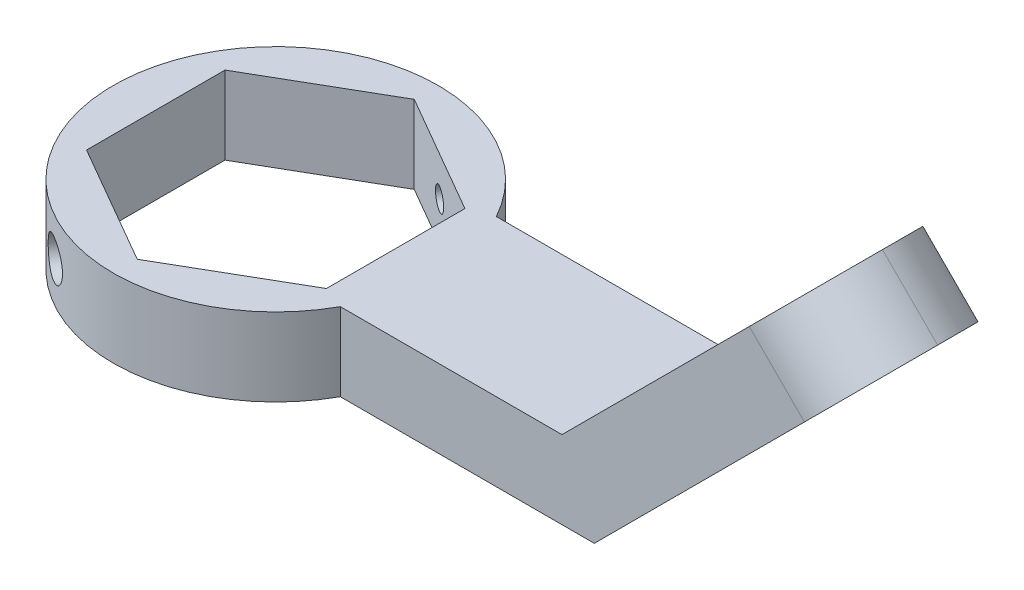
SolidWorks part; units mm, degrees
ref_plane "Front Plane" through (0, 0, 0) normal (0, 0, 1) x (1, 0, 0)
ref_plane "Top Plane" through (0, 0, 0) normal (0, 1, 0) x (1, 0, 0)
ref_plane "Right Plane" through (0, 0, 0) normal (1, 0, 0) x (0, 0, -1)
sketch "Sketch2" plane through (0, 0, 0) normal (0, 0, 1) x (1, 0, 0)
  line L0 (0, 0) -> (61, 0) construction
  line L1 (61, 0) -> (90.5, 29.5) construction
  dimension "D1" = 29.5
  dimension "D2" = 90.5
  dimension "D3" = 45
sketch "Sketch3" plane through (0, 0, 0) normal (0, 1, 0) x (1, 0, 0)
  line L1 (0, 21.3042) -> (-18.45, 10.6521)
  line L2 (-18.45, 10.6521) -> (-18.45, -10.6521)
  line L3 (-18.45, -10.6521) -> (0, -21.3042)
  line L4 (0, -21.3042) -> (18.45, -10.6521)
  line L5 (18.45, -10.6521) -> (18.45, 10.6521)
  line L6 (18.45, 10.6521) -> (0, 21.3042)
  line L7 (-11, -12) -> (61, -12)
  line L8 (-11, -12) -> (-11, 12)
  line L9 (-11, 12) -> (61, 12)
  line L10 (61, -12) -> (61, 12)
  line L11 (-11, -12) -> (61, 12) construction
  line L12 (-11, 12) -> (61, -12) construction
  circle A0 centre (0, 0) radius 18.45 construction
  circle A1 centre (0, 0) radius 25
  point P10 (25, 0)
  point P18 (61, 0)
  dimension "D1" = 36.9
  dimension "D2" = 50
  dimension "D3" = 24
extrude "Boss-Extrude1" add sketch "Sketch3" along normal blind 12 contours L9 A1 L7 L5 L4 L3 L2 L1 L6 | L7 A1 L9 L5 | A1 L7 L10 L9 region at (-9.5679, 0, -16.572) region at (21.217, 0, 0) region at (42.4908, 0, 0)
ref_plane "Plane1" through (30.5, -30.5, 0) normal (0.7071, -0.7071, 0) x (0.7071, 0.7071, 0)
sketch "Sketch4" plane through (30.5, -30.5, 0) normal (0.7071, -0.7071, 0) x (0.7071, 0.7071, 0)
  line L0 (43.1335, 0) -> (84.8528, 0) construction
  line L2 (43.1335, 12) -> (100.8528, 12)
  line L3 (43.1335, 12) -> (43.1335, -12)
  line L4 (43.1335, -12) -> (100.8528, -12)
  line L5 (100.8528, 12) -> (100.8528, -12)
  circle A0 centre (84.8528, 0) radius 8
  circle A1 centre (84.8528, 0) radius 4
  dimension "D1" = 16
  dimension "D2" = 8
  dimension "D3" = 24
  dimension "D4" = 16
extrude "Boss-Extrude2" add sketch "Sketch4" against normal blind 12 contours A1 | L2 L5 L4 L3 region at (90.5, 29.5, 0)
extrude "Cut-Extrude1" cut sketch "Sketch4<3>" against normal blind 5.15 contours A0 | A1
sketch "Sketch4<3>" plane through (30.5, -30.5, 0) normal (0.7071, -0.7071, 0) x (0.7071, 0.7071, 0) same geometry as "Sketch4"
fillet "Fillet1" radius 12 2 edges at (97.5711, 45.0563, -12) (97.5711, 45.0563, 12)
sketch "Sketch5" plane through (9.225, 0, -15.9782) normal (-0.5, 0, 0.866) x (0.866, 0, 0.5)
  line L0 (10.6521, 12) -> (-10.6521, 12) construction
  line L1 (10.6521, 12) -> (10.6521, 0) construction
  circle A0 centre (0, 6) radius 1.7
  circle A1 centre (0, 6) radius 3
  point P5 (0, 12)
  point P8 (10.6521, 6)
  dimension "D1" = 6
  dimension "D2" = 3.4
extrude "Cut-Extrude2" cut sketch "Sketch5" against normal through all contours A0 region at (9.225, 6, -15.9782)
extrude "Cut-Extrude3" cut sketch "Sketch5<3>" against normal through all from offset 5 contours A1 offset against normal yes
sketch "Sketch5<3>" plane through (9.225, 0, -15.9782) normal (-0.5, 0, 0.866) x (0.866, 0, 0.5) same geometry as "Sketch5"
ref_plane "Plane2" through (0, 0, 0) normal (-0.5, 0, 0.866) x (0.866, 0, 0.5)
mirror "Mirror1" about plane through (0, 0, 0) normal (-0.5, 0, 0.866) of "Cut-Extrude3", "Cut-Extrude2"
equation "\"hexD\"=36.9"
equation "\"D1@Sketch3\"=\"hexD\""
equation "\"D\"=50"
equation "\"D2@Sketch3\"=\"D\""
